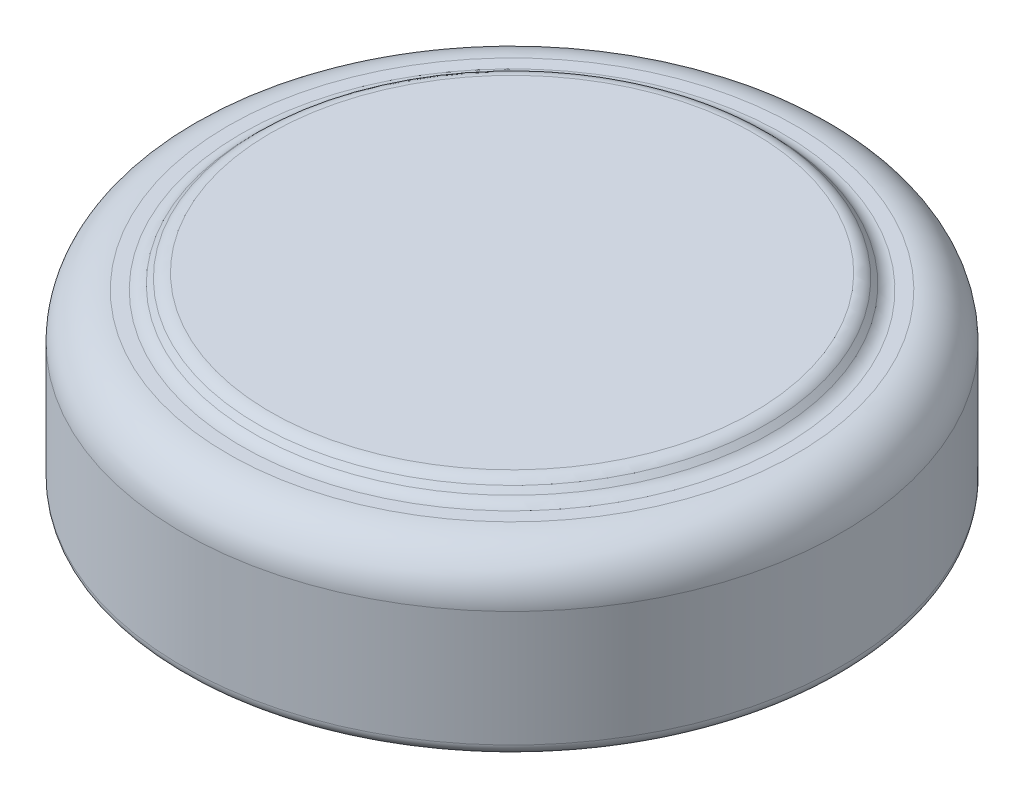
SolidWorks part; units mm, degrees
ref_plane "Front Plane" through (0, 0, 0) normal (0, 0, 1) x (1, 0, 0)
ref_plane "Top Plane" through (0, 0, 0) normal (0, 1, 0) x (1, 0, 0)
ref_plane "Right Plane" through (0, 0, 0) normal (1, 0, 0) x (0, 0, -1)
sketch "Sketch1" plane through (0, 0, 0) normal (0, 0, 1) x (1, 0, 0)
  line L0 (0, 0) -> (-2.8, 0)
  line L1 (-2.9, 0.1) -> (-2.9, 1.118)
  line L2 (-2.1259, 1.65) -> (0, 1.65)
  line L3 (0, 1.65) -> (0, 0)
  line L4 (-2.2761, 1.5619) -> (-2.2319, 1.6061)
  line L7 (-2.3821, 1.518) -> (-2.5, 1.518)
  arc A0 (-2.9, 1.118) -> (-2.5, 1.518) centre (-2.5, 1.118) cw
  arc A1 (-2.1259, 1.65) -> (-2.2319, 1.6061) centre (-2.1259, 1.5) ccw
  arc A2 (-2.3821, 1.518) -> (-2.2761, 1.5619) centre (-2.3821, 1.668) ccw
  arc A3 (-2.8, 0) -> (-2.9, 0.1) centre (-2.8, 0.1) cw
  point P9 (-2.9, 1.518)
  point P12 (-2.32, 1.518)
  point P13 (-2.32, 1.518)
  point P14 (-2.188, 1.65)
  point P17 (-2.9, 0)
  point P20 (-2.32, 1.518)
  dimension "D6" = 0.4
  dimension "D7" = 0.15
  dimension "D8" = 0.1
  dimension "D1" = 2.9
  dimension "D2" = 1.65
  dimension "D3" = 2.32
  dimension "D4" = 1.518
  dimension "D5" = 45
revolve "Revolve1" add sketch "Sketch1" angle 360 about L3
sketch "Sketch2" plane through (0, 0, 0) normal (0, -1, 0) x (1, 0, 0)
  line L0 (0.25, 0.25) -> (1.4, 0.25)
  line L1 (-0.25, 1.4) -> (0.25, 1.4)
  line L2 (-0.25, 1.4) -> (-0.25, 0.25)
  line L3 (-0.25, -1.4) -> (0.25, -1.4)
  line L4 (0.25, 1.4) -> (0.25, 0.25)
  line L5 (-1.4, 0.25) -> (-0.25, 0.25)
  line L6 (-1.4, 0.25) -> (-1.4, -0.25)
  line L7 (-1.4, -0.25) -> (-0.25, -0.25)
  line L8 (1.4, 0.25) -> (1.4, -0.25)
  line L9 (0.25, -0.25) -> (1.4, -0.25)
  line L10 (0.25, -0.25) -> (0.25, -1.4)
  line L11 (-0.25, -0.25) -> (-0.25, -1.4)
  circle A0 centre (0, 0) radius 1.75 construction
  text T0 "                   SR62" font "Century Gothic" height 0.75
  dimension "D1" = 3.5
  dimension "D2" = 0.5
  dimension "D3" = 0.5
  dimension "D4" = 0.25
  dimension "D5" = 0.25
  dimension "D6" = 2.8
  dimension "D7" = 2.8
  dimension "D8" = 1.4
  dimension "D9" = 1.4
wrap "Wrap1" sketch "Sketch2" wrap type scribe source sketch "Sketch2" face at (-2.8, 0, 0)
